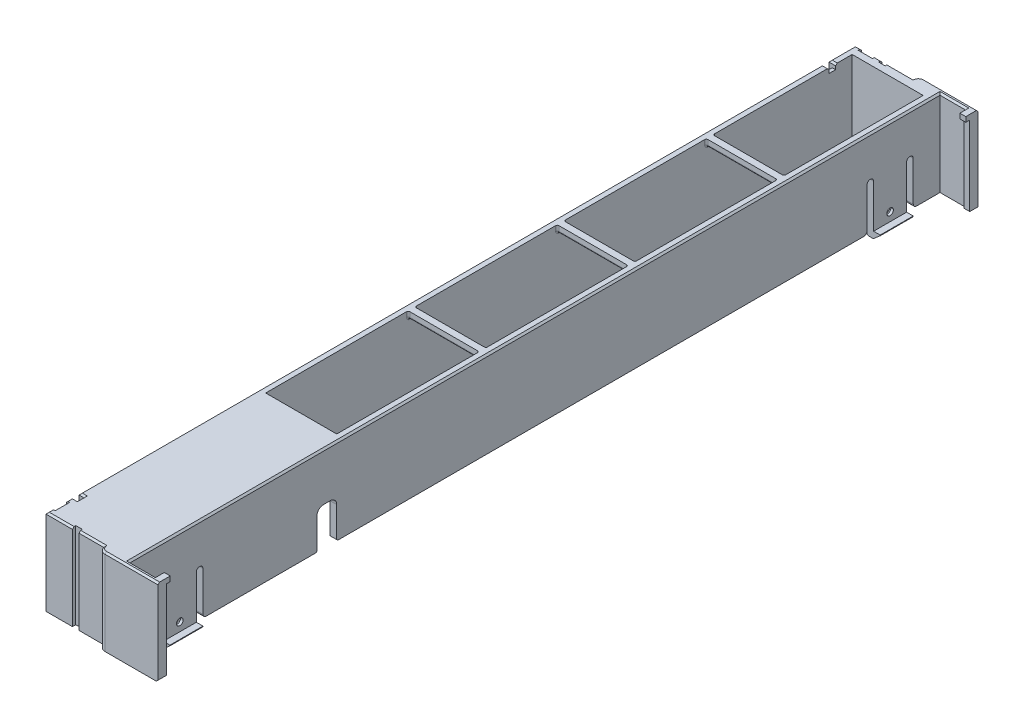
SolidWorks part; units mm, degrees
material "ABS"
ref_plane "Front Plane" through (0, 0, 0) normal (0, 0, 1) x (1, 0, 0)
ref_plane "Top Plane" through (0, 0, 0) normal (0, 1, 0) x (1, 0, 0)
ref_plane "Right Plane" through (0, 0, 0) normal (1, 0, 0) x (0, 0, -1)
sketch "Sketch1" plane through (0, 0, 0) normal (0, 1, 0) x (1, 0, 0)
  line L1 (12.75, -122.5) -> (-12.75, -122.5)
  line L2 (12.75, -122.5) -> (12.75, 122.5)
  line L3 (12.75, 122.5) -> (-12.75, 122.5)
  line L4 (-12.75, -122.5) -> (-12.75, 122.5)
  line L5 (12.75, -122.5) -> (-12.75, 122.5) construction
  line L6 (12.75, 122.5) -> (-12.75, -122.5) construction
  line L7 (10.75, -120.5) -> (-10.75, -120.5)
  line L8 (10.75, -120.5) -> (10.75, 120.5)
  line L9 (10.75, 120.5) -> (-10.75, 120.5)
  line L10 (-10.75, -120.5) -> (-10.75, 120.5)
  line L11 (10.75, -120.5) -> (-10.75, 120.5) construction
  line L12 (10.75, 120.5) -> (-10.75, -120.5) construction
  point P0 (0, 0)
  point P6 (0, 0)
  dimension "D1" = 245
  dimension "D2" = 25.5
  dimension "D3" = 2
  dimension "D4" = 2
extrude "Boss-Extrude1" add sketch "Sketch1" along normal blind 26
ref_plane "Plane1" through (0, 0, 0) normal (0, 0, 1) x (1, 0, 0)
ref_plane "Plane2" through (0, 0, 0) normal (-1, 0, 0) x (0, 0, 1)
sketch "Sketch5" plane through (0, 0, 122.5) normal (0, 0, 1) x (1, 0, 0)
  line L0 (-11.75, 26) -> (-11.75, 0) construction
  line L1 (-12.75, 25) -> (-11.75, 26)
  line L4 (-11.75, 26) -> (-13.75, 26)
  line L5 (-12.75, 25) -> (-11.75, 24)
  line L6 (-11.75, 24) -> (-12.75, 23)
  line L7 (-12.75, 23) -> (-11.75, 22)
  line L8 (-11.75, 22) -> (-12.75, 21)
  line L9 (-12.75, 21) -> (-11.75, 20)
  line L10 (-11.75, 20) -> (-12.75, 19)
  line L11 (-12.75, 19) -> (-11.75, 18)
  line L12 (-11.75, 18) -> (-12.75, 17)
  line L13 (-12.75, 17) -> (-11.75, 16)
  line L14 (-11.75, 16) -> (-12.75, 15)
  line L15 (-12.75, 15) -> (-11.75, 14)
  line L16 (-11.75, 14) -> (-12.75, 13)
  line L17 (-12.75, 13) -> (-11.75, 12)
  line L18 (-11.75, 12) -> (-12.75, 11)
  line L19 (-12.75, 11) -> (-11.75, 10)
  line L20 (-11.75, 10) -> (-12.75, 9)
  line L21 (-12.75, 9) -> (-11.75, 8)
  line L22 (-11.75, 8) -> (-12.75, 7)
  line L23 (-12.75, 7) -> (-11.75, 6)
  line L24 (-13.75, 0) -> (-13.75, 26)
  line L26 (-11.75, 6) -> (-12.75, 5)
  line L27 (-12.75, 5) -> (-11.75, 4)
  line L28 (-11.75, 4) -> (-12.75, 3)
  line L29 (-12.75, 3) -> (-11.75, 2)
  line L30 (-12.75, 25) -> (-12.75, 0) construction
  line L31 (-11.75, 2) -> (-12.75, 1)
  line L32 (-12.75, 1) -> (-11.75, 0)
  line L33 (-11.75, 0) -> (-13.75, 0)
  dimension "D1" = 45
  dimension "D2" = 1
  dimension "D3" = 1
  dimension "D4" = 2
  dimension "D5" = 26
extrude "Cut-Extrude4" cut sketch "Sketch5" against normal blind 4.4 from offset 1.8 offset against normal yes
sketch "Sketch8" plane through (-12.75, 0, 0) normal (-1, 0, 0) x (0, 0, 1)
  line L0 (-121.5, 26) -> (-121.5, 0) construction
  line L1 (-122.5, 25) -> (-121.5, 26)
  line L2 (-121.5, 26) -> (-123.5, 26)
  line L3 (-122.5, 25) -> (-121.5, 24)
  line L4 (-121.5, 24) -> (-122.5, 23)
  line L5 (-122.5, 23) -> (-121.5, 22)
  line L6 (-121.5, 22) -> (-122.5, 21)
  line L7 (-122.5, 21) -> (-121.5, 20)
  line L8 (-121.5, 20) -> (-122.5, 19)
  line L9 (-122.5, 19) -> (-121.5, 18)
  line L10 (-121.5, 18) -> (-122.5, 17)
  line L11 (-122.5, 17) -> (-121.5, 16)
  line L12 (-121.5, 16) -> (-122.5, 15)
  line L13 (-122.5, 15) -> (-121.5, 14)
  line L14 (-121.5, 14) -> (-122.5, 13)
  line L15 (-122.5, 13) -> (-121.5, 12)
  line L16 (-121.5, 12) -> (-122.5, 11)
  line L17 (-122.5, 11) -> (-121.5, 10)
  line L18 (-121.5, 10) -> (-122.5, 9)
  line L19 (-122.5, 9) -> (-121.5, 8)
  line L20 (-121.5, 8) -> (-122.5, 7)
  line L21 (-122.5, 7) -> (-121.5, 6)
  line L22 (-123.5, 0) -> (-123.5, 26)
  line L23 (-121.5, 6) -> (-122.5, 5)
  line L24 (-122.5, 5) -> (-121.5, 4)
  line L25 (-121.5, 4) -> (-122.5, 3)
  line L26 (-122.5, 3) -> (-121.5, 2)
  line L27 (-122.5, 25) -> (-122.5, 0) construction
  line L28 (-121.5, 2) -> (-122.5, 1)
  line L32 (-122.5, 1) -> (-121.5, 0)
  line L33 (-121.5, 0) -> (-123.5, 0)
  dimension "D1" = 45
  dimension "D2" = 1
  dimension "D3" = 1
  dimension "D4" = 2
  dimension "D5" = 26
extrude "Cut-Extrude5" cut sketch "Sketch8" against normal blind 4.4 from offset 1.8 offset against normal yes
sketch "Sketch10" plane through (0, 26, 0) normal (0, 1, 0) x (1, 0, 0)
  line L0 (12.75, 122.5) -> (-6.55, 122.5) construction
  line L1 (4.75, 122.5) -> (12.75, 122.5)
  line L2 (4.75, 122.5) -> (4.75, 124.1)
  line L3 (4.75, 124.1) -> (22.75, 124.1)
  line L4 (12.75, 122.5) -> (12.75, 122.6)
  line L6 (20.95, -122.6) -> (20.95, -121.6)
  line L7 (22.75, -121.6) -> (20.95, -121.6)
  line L8 (22.75, -124.1) -> (22.75, -121.6)
  line L9 (12.75, -122.6) -> (20.95, -122.6)
  line L10 (12.75, -122.5) -> (12.75, 122.5) construction
  line L11 (12.75, 0) -> (-12.75, 0) construction
  line L12 (12.75, -122.5) -> (12.75, -122.6)
  line L13 (4.75, -124.1) -> (22.75, -124.1)
  line L14 (12.75, 122.6) -> (20.95, 122.6)
  line L15 (4.75, -122.5) -> (4.75, -124.1)
  line L16 (4.75, -122.5) -> (12.75, -122.5)
  line L17 (22.75, 124.1) -> (22.75, 121.6)
  line L18 (22.75, 121.6) -> (20.95, 121.6)
  line L19 (20.95, 122.6) -> (20.95, 121.6)
  line L20 (-12.75, 122.5) -> (-12.75, -116.3) construction
  dimension "D1" = 248.2
  dimension "D2" = 8
  dimension "D3" = 245.2
  dimension "D4" = 8.2
  dimension "D5" = 1.8
  dimension "D6" = 243.2
extrude "Boss-Extrude3" add sketch "Sketch10" against normal up to surface (26 mm away) up to face at (-7, 0, -1.1667)
fillet "Fillet1" radius 2 2 edges at (4.75, 13, 124.1) (4.75, 13, -124.1)
sketch "Sketch11" plane through (12.75, 0, 0) normal (1, 0, 0) x (0, 0, -1)
  line L0 (-122.6, 0) -> (122.6, 0) construction
  line L1 (-114.5, 0) -> (-114.5, 14)
  line L2 (-112.5, 14) -> (-114.5, 14)
  line L3 (-112.5, 0) -> (-112.5, 14)
  line L4 (-112.5, 0) -> (-114.5, 0)
  line L5 (0, 0) -> (0, 26) construction
  line L6 (-102.5, 0) -> (-102.5, 14)
  line L7 (-100.5, 14) -> (-102.5, 14)
  line L8 (-100.5, 0) -> (-100.5, 14)
  line L9 (-100.5, 0) -> (-102.5, 0)
  line L14 (-122.6, 26) -> (122.6, 26) construction
  line L17 (-121.6, 13) -> (121.6, 13) construction
  line L18 (-121.6, 0) -> (-121.6, 26) construction
  line L19 (121.6, 0) -> (121.6, 26) construction
  line L20 (120.5, 26) -> (120.5, 0) construction
  line L21 (100.5, 0) -> (102.5, 0)
  line L22 (100.5, 0) -> (100.5, 14)
  line L23 (100.5, 14) -> (102.5, 14)
  line L24 (102.5, 0) -> (102.5, 14)
  line L25 (112.5, 0) -> (114.5, 0)
  line L26 (112.5, 0) -> (112.5, 14)
  line L27 (112.5, 14) -> (114.5, 14)
  line L28 (114.5, 0) -> (114.5, 14)
  dimension "D4" = 2
  dimension "D5" = 10
  dimension "D6" = 6
  dimension "D7" = 1
extrude "Cut-Extrude6" cut sketch "Sketch11" against normal up to next
fillet "Fillet2" radius 1 12 edges at (11.75, 14, -112.5) (11.75, 14, -100.5) (11.75, 0, -100.5) (11.75, 0, -114.5) (11.75, 14, -102.5) (11.75, 14, -114.5) (11.75, 0, 100.5) (11.75, 0, 114.5) (11.75, 14, 102.5) (11.75, 14, 100.5) (11.75, 14, 112.5) (11.75, 14, 114.5)
sketch "Sketch12" plane through (12.75, 0, 0) normal (1, 0, 0) x (0, 0, -1)
  line L1 (-112.5, 0) -> (-102.5, 0)
  line L2 (-112.5, 0) -> (-112.5, -2.1)
  line L3 (-112.5, -2.1) -> (-102.5, -2.1)
  line L4 (-102.5, 0) -> (-102.5, -2.1)
  line L5 (112.5, 0) -> (102.5, 0)
  line L6 (112.5, 0) -> (112.5, -2.1)
  line L7 (112.5, -2.1) -> (102.5, -2.1)
  line L8 (102.5, 0) -> (102.5, -2.1)
  line L10 (102.5, 0) -> (102.5, 13) construction
  dimension "D1" = 2.1
extrude "Boss-Extrude4" add sketch "Sketch12" against normal up to surface (2 mm away) up to face at (10.75, 7.7439, 0)
sketch "Sketch13" plane through (12.75, 0, 0) normal (1, 0, 0) x (0, 0, -1)
  line L0 (-102.5, 13) -> (-102.5, -2.1) construction
  line L1 (-112.5, -2.1) -> (-102.5, -2.1)
  line L2 (-112.5, -2.1) -> (-112.5, -0.1)
  line L3 (-112.5, -0.1) -> (-102.5, -0.1)
  line L4 (-102.5, -2.1) -> (-102.5, -0.1)
  line L5 (112.5, 13) -> (112.5, -2.1) construction
  line L6 (102.5, -2.1) -> (112.5, -2.1)
  line L7 (102.5, -2.1) -> (102.5, -0.1)
  line L8 (102.5, -0.1) -> (112.5, -0.1)
  line L9 (112.5, -2.1) -> (112.5, -0.1)
  line L10 (102.5, -2.1) -> (112.5, -2.1) construction
  dimension "D1" = 2
extrude "Boss-Extrude5" add sketch "Sketch13" along normal blind 2
chamfer "Chamfer1" distance 2.1 distance2 1.8 2 edges at (14.75, -2.1, -107.5) (14.75, -2.1, 107.5) first distance on face at (12.75, -2.1, -107.5) first distance on face at (12.75, -2.1, 107.5)
sketch "Sketch15" plane through (0, 26, 0) normal (0, 1, 0) x (1, 0, 0)
  line L0 (-12.75, 122.5) -> (-12.75, -116.3) construction
  line L1 (-12.75, -112.5) -> (-11.75, -112.5)
  line L2 (-12.75, -112.5) -> (-12.75, -114.5)
  line L3 (-12.75, -114.5) -> (-11.75, -114.5)
  line L4 (-11.75, -112.5) -> (-11.75, -114.5)
  line L5 (-12.75, -122.5) -> (4.75, -122.5) construction
  line L6 (-4.75, -122.5) -> (-2.75, -122.5)
  line L7 (-4.75, -122.5) -> (-4.75, -121.5)
  line L8 (-4.75, -121.5) -> (-2.75, -121.5)
  line L9 (-2.75, -122.5) -> (-2.75, -121.5)
  line L10 (12.75, 0) -> (-12.75, 0) construction
  line L11 (12.75, -122.6) -> (12.75, 122.6) construction
  line L12 (-12.25, -114.5) -> (-12.25, -122.5) construction
  line L13 (-4.75, -122) -> (-12.75, -122) construction
  line L14 (-12.75, -120.7) -> (-12.75, -122.5) construction
  line L15 (-4.75, 122) -> (-12.75, 122) construction
  line L16 (-12.25, 114.5) -> (-12.25, 122.5) construction
  line L17 (-2.75, 122.5) -> (-2.75, 121.5)
  line L18 (-4.75, 121.5) -> (-2.75, 121.5)
  line L19 (-4.75, 122.5) -> (-4.75, 121.5)
  line L20 (-4.75, 122.5) -> (-2.75, 122.5)
  line L21 (-11.75, 112.5) -> (-11.75, 114.5)
  line L22 (-12.75, 114.5) -> (-11.75, 114.5)
  line L23 (-12.75, 112.5) -> (-12.75, 114.5)
  line L24 (-12.75, 112.5) -> (-11.75, 112.5)
  dimension "D1" = 2
  dimension "D2" = 1
  dimension "D3" = 8
extrude "Cut-Extrude7" cut sketch "Sketch15" against normal up to surface (26 mm away) up to face at (5.0047, 0, -0.4375)
sketch "Sketch16" plane through (0, 26, 0) normal (0, 1, 0) x (1, 0, 0)
  line L0 (12.75, 0) -> (-12.75, 0) construction
  line L1 (20.95, 121.6) -> (22.75, 121.6)
  line L2 (20.95, 121.6) -> (20.95, 120.4)
  line L3 (20.95, 120.4) -> (22.75, 120.4)
  line L4 (22.75, 121.6) -> (22.75, 120.4)
  line L5 (12.75, -122.6) -> (12.75, 122.6) construction
  line L6 (-12.75, 112.5) -> (-12.75, -112.5) construction
  line L7 (22.75, -121.6) -> (22.75, -120.4)
  line L8 (20.95, -120.4) -> (22.75, -120.4)
  line L9 (20.95, -121.6) -> (20.95, -120.4)
  line L10 (20.95, -121.6) -> (22.75, -121.6)
  dimension "D1" = 240.8
extrude "Boss-Extrude7" add sketch "Sketch16" against normal blind 1.5
chamfer "Chamfer2" distance 0.5 angle 45 22 edges at (5.4447, 26, -123.6492) (14.7298, 26, -124.1) (1, 26, -122.5) (-5.65, 26, -122.5) (-11.85, 26, -122.5) (-12.75, 26, -118.5) (-12.75, 26, 0) (-12.75, 26, 115.4) (-12.75, 26, 121.6) (-8.75, 26, 122.5) (5.4447, 26, 123.6492) (14.7298, 26, 124.1) (1, 26, 122.5) (22.75, 0, -122.85) (20.95, 0, -122.1) (21.85, 0, -121.6) (22.75, 0, 122.85) (20.95, 0, 122.1) (21.85, 0, 121.6) (16.85, 26, -122.6) (16.85, 26, 122.6) (12.75, 26, 0)
sketch "Sketch18" plane through (10.75, 0, 0) normal (-1, 0, 0) x (0, 0, 1)
  line L0 (120.5, 26) -> (-120.5, 26) construction
  line L1 (60, 26) -> (58, 26)
  line L2 (60, 26) -> (60, 13)
  line L3 (60, 13) -> (58, 13)
  line L4 (58, 26) -> (58, 13)
  line L5 (120.5, 26) -> (120.5, 0) construction
  line L6 (120.5, 13) -> (60, 13) construction
  dimension "D1" = 2
  dimension "D2" = 60.5
extrude "Boss-Extrude9" add sketch "Sketch18" along normal up to surface (21.5 mm away) up to face at (-10.75, 13, 0)
sketch "Sketch19" plane through (0, 26, 0) normal (0, 1, 0) x (1, 0, 0)
  line L1 (10.75, -58) -> (11.75, -58)
  line L2 (10.75, -58) -> (10.75, 120.5)
  line L3 (10.75, 120.5) -> (11.75, 120.5)
  line L4 (11.75, -58) -> (11.75, 120.5)
  dimension "D1" = 1
extrude "Cut-Extrude8" cut sketch "Sketch19" against normal up to surface (28.1 mm away) up to face at (11.7, -2.1, -107.5)
sketch "Sketch21" plane through (0, 26, 0) normal (0, 1, 0) x (1, 0, 0)
  line L0 (11.75, -58) -> (11.75, 120.5) construction
  line L1 (-10.75, -60) -> (10.75, -60)
  line L2 (-10.75, -60) -> (-10.75, -120.5)
  line L3 (-10.75, -120.5) -> (10.75, -120.5)
  line L4 (10.75, -60) -> (10.75, -120.5)
  line L5 (11.75, -14.875) -> (-10.75, -14.875)
  line L6 (11.75, -14.875) -> (11.75, -12.875)
  line L7 (11.75, -12.875) -> (-10.75, -12.875)
  line L8 (-10.75, -14.875) -> (-10.75, -12.875)
  line L9 (-10.75, 120.5) -> (-10.75, -58) construction
  line L10 (0.5, 75.375) -> (0.5, 32.25) construction
  line L11 (11.75, 30.25) -> (-10.75, 30.25)
  line L12 (11.75, 30.25) -> (11.75, 32.25)
  line L13 (11.75, 32.25) -> (-10.75, 32.25)
  line L14 (-10.75, 30.25) -> (-10.75, 32.25)
  line L15 (11.75, 75.375) -> (-10.75, 75.375)
  line L16 (11.75, 75.375) -> (11.75, 77.375)
  line L17 (11.75, 77.375) -> (-10.75, 77.375)
  line L18 (-10.75, 75.375) -> (-10.75, 77.375)
  line L19 (0.5, -12.875) -> (0.5, 30.25) construction
  line L20 (0.5, -14.875) -> (0.5, -58) construction
  line L21 (-10.75, -58) -> (11.75, -58) construction
  line L22 (0.5, 77.375) -> (0.5, 120.5) construction
  line L23 (11.75, 120.5) -> (-10.75, 120.5) construction
  dimension "D1" = 2
extrude "Boss-Extrude11" add sketch "Sketch21" against normal blind 2
sketch "Sketch22" plane through (0, 0, 58) normal (0, 0, -1) x (-1, 0, 0)
  line L0 (0, 26) -> (0, 13) construction
  line L5 (10.75, 13) -> (-10.75, 13) construction
  line L6 (10.75, 26) -> (-11.75, 26) construction
  circle A0 centre (0, 13) radius 1.5
  dimension "D1" = 3
extrude "Cut-Extrude9" cut sketch "Sketch22" against normal up to next
sketch "Sketch23" plane through (0, 0, -120.5) normal (0, 0, 1) x (1, 0, 0)
  circle A0 centre (0, 13) radius 1.5
  dimension "D1" = 3
extrude "Cut-Extrude10" cut sketch "Sketch23" against normal up to surface (2 mm away) up to face at (1, 12.75, -122.5)
sketch "Sketch24" plane through (0, 26, 0) normal (0, 1, 0) x (1, 0, 0)
  line L0 (-10.75, 120.5) -> (-10.75, 77.375) construction
  line L1 (-11.75, 114.5) -> (-10.75, 114.5)
  line L2 (-11.75, 114.5) -> (-11.75, 112.5)
  line L3 (-11.75, 112.5) -> (-10.75, 112.5)
  line L4 (-10.75, 114.5) -> (-10.75, 112.5)
  line L6 (-11.75, -112.5) -> (-10.75, -112.5)
  line L7 (-11.75, -112.5) -> (-11.75, -114.5)
  line L8 (-11.75, -114.5) -> (-10.75, -114.5)
  line L9 (-10.75, -112.5) -> (-10.75, -114.5)
extrude "Cut-Extrude11" cut sketch "Sketch24" against normal blind 1.5
chamfer "Chamfer3" distance 0.5 angle 45 4 edges at (-11.5, 26, -114.5) (-11.5, 26, -112.5) (-11.5, 26, 112.5) (-11.5, 26, 114.5)
sketch "Sketch25" plane through (0, 24, 0) normal (0, -1, 0) x (1, 0, 0)
  line L0 (10.75, 120.5) -> (10.75, 60) construction
  line L1 (10.75, 72) -> (-10.75, 72)
  line L2 (10.75, 72) -> (10.75, 70)
  line L3 (10.75, 70) -> (-10.75, 70)
  line L4 (-10.75, 72) -> (-10.75, 70)
  line L5 (-10.75, 60) -> (-10.75, 120.5) construction
  line L6 (10.75, 60) -> (-10.75, 60) construction
  dimension "D1" = 2
  dimension "D2" = 10
extrude "Boss-Extrude12" add sketch "Sketch25" along normal up to surface (24 mm away) up to face at (11.75, 0, 19.3333)
sketch "Sketch26" plane through (0, 0, 0) normal (0, -1, 0) x (1, 0, 0)
  line L0 (-10.75, 72) -> (10.75, 72) construction
  line L1 (7.5, 72) -> (-7.5, 72)
  line L2 (7.5, 72) -> (7.5, 70)
  line L3 (7.5, 70) -> (-7.5, 70)
  line L4 (-7.5, 72) -> (-7.5, 70)
  line L5 (10.75, 70) -> (-10.75, 70) construction
  line L6 (0, 72) -> (0, 70) construction
  dimension "D1" = 15
extrude "Cut-Extrude12" cut sketch "Sketch26" against normal blind 1.5
sketch "Sketch27" plane through (0, 1.5, 0) normal (0, -1, 0) x (1, 0, 0)
  line L0 (-7.5, 70) -> (7.5, 70) construction
  line L1 (3, 70) -> (-3, 70)
  line L2 (3, 70) -> (3, 67)
  line L3 (3, 67) -> (-3, 67)
  line L4 (-3, 70) -> (-3, 67)
  line L5 (0, 72) -> (0, 67) construction
  line L6 (7.5, 72) -> (-7.5, 72) construction
  dimension "D1" = 5
  dimension "D2" = 6
extrude "Boss-Extrude13" add sketch "Sketch27" against normal up to surface (22.5 mm away) up to face at (0, 24, 65)
fillet "Fillet5" radius 3 2 edges at (3, 12.75, 67) (-3, 12.75, 67)
sketch "Sketch28" plane through (0, 1.5, 0) normal (0, -1, 0) x (1, 0, 0)
  line L0 (0, 67) -> (0, 72) construction
  line L1 (7.5, 72) -> (-7.5, 72) construction
  circle A0 centre (0, 69.5) radius 0.9
  circle A1 centre (32.7502, 69) radius 0.9 construction
extrude "Cut-Extrude13" cut sketch "Sketch28" against normal blind 6
sketch "Sketch29" plane through (0, 13, 0) normal (0, -1, 0) x (1, 0, 0)
  line L0 (-10.75, 60) -> (-1.5, 60) construction
  line L1 (10.75, 60) -> (5.75, 60)
  line L2 (10.75, 60) -> (10.75, 59)
  line L3 (10.75, 59) -> (5.75, 59)
  line L4 (5.75, 60) -> (5.75, 59)
  line L5 (-5.75, 60) -> (-10.75, 60)
  line L6 (-5.75, 60) -> (-5.75, 59)
  line L7 (-5.75, 59) -> (-10.75, 59)
  line L8 (-10.75, 60) -> (-10.75, 59)
  line L9 (-10.75, 60) -> (-10.75, 58) construction
  line L10 (10.75, 58) -> (10.75, 60) construction
  dimension "D1" = 5
extrude "Cut-Extrude14" cut sketch "Sketch29" against normal blind 3
sketch "Sketch30" plane through (10.75, 0, 0) normal (-1, 0, 0) x (0, 0, 1)
  line L1 (60, 0) -> (66, 0)
  line L2 (60, 0) -> (60, 11.5)
  line L3 (60, 11.5) -> (66, 11.5)
  line L4 (66, 0) -> (66, 11.5)
  line L5 (70, 0) -> (58, 0) construction
  line L6 (60, 16) -> (60, 24) construction
  dimension "D1" = 6
  dimension "D2" = 0
  dimension "D3" = 11.5
extrude "Cut-Extrude15" cut sketch "Sketch30" against normal up to next
fillet "Fillet6" radius 2 2 edges at (11.75, 11.5, 66) (11.75, 11.5, 60)
chamfer "Chamfer4" distance 0.3 angle 45 4 edges at (11.75, 0, 66) (11.75, 0, 60) (7.5, 0, 71) (-7.5, 0, 71)
sketch "Sketch32" plane through (11.75, 0, 0) normal (-1, 0, 0) x (0, 0, 1)
  line L9 (-120.5, 26) -> (58, 26)
  line L18 (-120.5, 26) -> (-120.5, 0)
  line L19 (-120.5, 0) -> (-115.5, 0)
  line L20 (-114.5, 1) -> (-114.5, 13)
  line L21 (-112.5, 13) -> (-112.5, -2.1)
  line L22 (-112.5, -2.1) -> (-102.5, -2.1)
  line L23 (-102.5, -2.1) -> (-102.5, 13)
  line L24 (-100.5, 13) -> (-100.5, 1)
  line L25 (-99.5, 0) -> (58, 0)
  line L26 (58, 0) -> (58, 26)
  line L27 (-120.5, 26) -> (-120.5, 0)
  line L28 (-120.5, 0) -> (-115.5, 0)
  line L29 (-114.5, 1) -> (-114.5, 13)
  line L30 (-112.5, 13) -> (-112.5, -2.1)
  line L31 (-112.5, -2.1) -> (-102.5, -2.1)
  line L32 (-102.5, -2.1) -> (-102.5, 13)
  line L33 (-100.5, 13) -> (-100.5, 1)
  line L34 (-99.5, 0) -> (58, 0)
  line L35 (58, 0) -> (58, 26)
  arc A12 (-115.5, 0) -> (-114.5, 1) centre (-115.5, 1) ccw
  arc A13 (-113.5, 14) -> (-114.5, 13) centre (-113.5, 13) ccw
  arc A14 (-112.5, 13) -> (-113.5, 14) centre (-113.5, 13) ccw
  arc A15 (-101.5, 14) -> (-102.5, 13) centre (-101.5, 13) ccw
  arc A16 (-100.5, 13) -> (-101.5, 14) centre (-101.5, 13) ccw
  arc A17 (-100.5, 1) -> (-99.5, 0) centre (-99.5, 1) ccw
  arc A18 (-115.5, 0) -> (-114.5, 1) centre (-115.5, 1) ccw
  arc A19 (-113.5, 14) -> (-114.5, 13) centre (-113.5, 13) ccw
  arc A20 (-112.5, 13) -> (-113.5, 14) centre (-113.5, 13) ccw
  arc A21 (-101.5, 14) -> (-102.5, 13) centre (-101.5, 13) ccw
  arc A22 (-100.5, 13) -> (-101.5, 14) centre (-101.5, 13) ccw
  arc A23 (-100.5, 1) -> (-99.5, 0) centre (-99.5, 1) ccw
  dimension "D1" = 0
extrude "Boss-Extrude14" add sketch "Sketch32" along normal blind 1
fillet "Fillet3" radius 0.5 2 edges at (10.75, -2.1, 107.5) (10.75, -2.1, -107.5)
sketch "Sketch31" plane through (10.75, 0, 0) normal (-1, 0, 0) x (0, 0, 1)
  line L0 (-107.5, -1.6) -> (-107.5, 2.5) construction
  line L2 (-112.5, 0) -> (112.5, 0) construction
  line L3 (107.5, -1.6) -> (107.5, 2.5) construction
  line L4 (102.5, -1.6) -> (112.5, -1.6) construction
  line L5 (107.5, 2.5) -> (-107.5, 2.5) construction
  line L6 (-112.5, -1.6) -> (-102.5, -1.6) construction
  circle A0 centre (-107.5, 2.5) radius 1
  circle A1 centre (107.5, 2.5) radius 1
  dimension "D1" = 2
  dimension "D2" = 2.5
extrude "Cut-Extrude16" cut sketch "Sketch31" against normal up to next
fillet "Fillet7" radius 0.5 24 edges at (-10.75, 25, -77.375) (-10.75, 25, -32.25) (-10.75, 25, 12.875) (-10.75, 24, -76.375) (-10.75, 24, -31.25) (-10.75, 24, 13.875) (10.75, 24, -76.375) (10.75, 24, -31.25) (10.75, 24, 13.875) (-10.75, 25, -75.375) (-10.75, 25, -30.25) (-10.75, 25, 14.875) (0, 24, 12.875) (10.75, 25, 12.875) (0, 24, -32.25) (10.75, 25, -32.25) (0, 24, -77.375) (10.75, 25, -77.375) (0, 24, -75.375) (0, 24, -30.25) (0, 24, 14.875) (10.75, 25, 14.875) (10.75, 25, -30.25) (10.75, 25, -75.375)
chamfer "Chamfer5" distance 1.2 angle 45 2 edges at (10.75, 2.5, -106.5) (10.75, 2.5, 108.5)
sketch "Sketch33" plane through (-12.75, 0, 0) normal (-1, 0, 0) x (0, 0, 1)
  circle A0 centre (107.5, 2.5) radius 0.9
  dimension "D1" = 1.8
extrude "Cut-Extrude17" cut sketch "Sketch33" against normal up to next
sketch "Sketch34" plane through (0, 0, -120.5) normal (0, 0, 1) x (1, 0, 0)
  line L8 (10.75, 0) -> (10.75, 26)
  line L9 (10.75, 26) -> (-10.75, 26)
  line L10 (-10.75, 26) -> (-10.75, 0)
  line L11 (-10.75, 0) -> (10.75, 0)
  line L12 (10.75, 0) -> (10.75, 26)
  line L13 (10.75, 26) -> (-10.75, 26)
  line L14 (-10.75, 26) -> (-10.75, 0)
  line L15 (-10.75, 0) -> (10.75, 0)
  circle A2 centre (0, 13) radius 1.5
  circle A3 centre (0, 13) radius 1.5
  dimension "D1" = 0
  dimension "D2" = 0
extrude "Boss-Extrude15" add sketch "Sketch34" along normal blind 1
